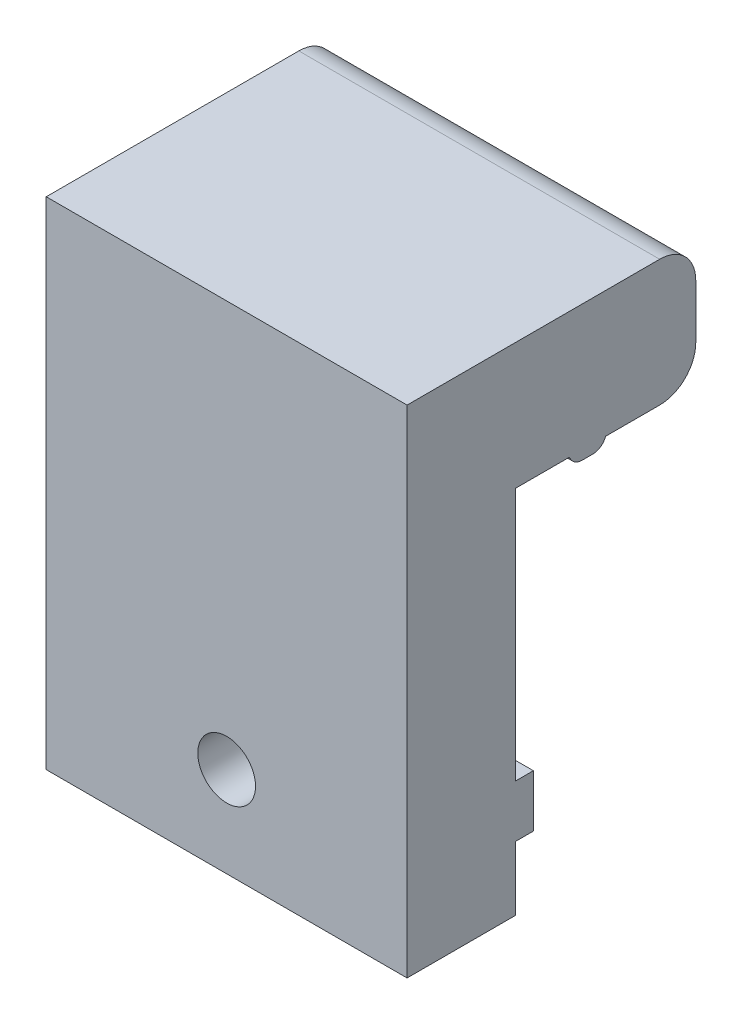
SolidWorks part; units mm, degrees
ref_plane "Front Plane" through (0, 0, 0) normal (0, 0, 1) x (1, 0, 0)
ref_plane "Top Plane" through (0, 0, 0) normal (0, 1, 0) x (1, 0, 0)
ref_plane "Right Plane" through (0, 0, 0) normal (1, 0, 0) x (0, 0, -1)
sketch "Esquisse1" plane through (0, 0, 0) normal (0, 0, 1) x (1, 0, 0)
  line L0 (-10, -13.75) -> (10, -13.75)
  line L1 (10, -13.75) -> (10, 13.75)
  line L2 (10, 13.75) -> (-10, 13.75)
  line L3 (-10, 13.75) -> (-10, -13.75)
  point P3 (0, 13.75)
  point P7 (-10, 0)
  dimension "D1" = 20
  dimension "D2" = 27.5
extrude "Boss.-Extru.1" add sketch "Esquisse1" along normal blind 6
sketch "Esquisse2" plane through (0, 0, 0) normal (0, 0, -1) x (-1, 0, 0)
  line L0 (10, 13.75) -> (10, -13.75) construction
  line L1 (-10, 13.75) -> (10, 13.75)
  line L2 (-10, 13.75) -> (-10, 6.75)
  line L3 (-10, 6.75) -> (10, 6.75)
  line L4 (10, 13.75) -> (10, 6.75)
  dimension "D1" = 7
extrude "Boss.-Extru.2" add sketch "Esquisse2" along normal blind 10
fillet "Congé2" radius 2 2 edges at (0, 6.75, -10) (0, 13.75, -10)
sketch "Esquisse3" plane through (0, 0, 0) normal (0, 0, -1) x (-1, 0, 0)
  line L0 (-10, -13.75) -> (-10, 6.75) construction
  line L1 (-10, -10.2) -> (10, -10.2)
  line L2 (-10, -10.2) -> (-10, -7.3)
  line L3 (-10, -7.3) -> (10, -7.3)
  line L4 (10, -10.2) -> (10, -7.3)
  line L5 (10, 6.75) -> (10, -13.75) construction
  line L6 (10, -13.75) -> (-10, -13.75) construction
  point P8 (-10, -8.75)
  dimension "D1" = 5
  dimension "D2" = 2.9
extrude "Boss.-Extru.3" add sketch "Esquisse3" along normal blind 1
sketch "Esquisse4" plane through (0, 0, 6) normal (0, 0, 1) x (1, 0, 0)
  line L0 (-10, -13.75) -> (10, -13.75) construction
  circle A0 centre (0, -8.75) radius 1.6
  point P5 (0, -13.75)
  dimension "D1" = 3.2
  dimension "D2" = 5
extrude "Enlèv. mat.-Extru.1" cut sketch "Esquisse4" against normal through all
sketch "Esquisse6" plane through (0, 6.75, 0) normal (0, -1, 0) x (1, 0, 0)
  line L0 (-10, -8) -> (-10, 0) construction
  line L1 (10, -3) -> (-10, -3)
  line L2 (10, -3) -> (10, -5)
  line L3 (10, -5) -> (-10, -5)
  line L4 (-10, -3) -> (-10, -5)
  line L5 (10, -8) -> (10, 0) construction
  point P11 (10, -4)
  point P12 (10, -4)
  dimension "D1" = 2
extrude "Boss.-Extru.5" add sketch "Esquisse6" along normal blind 0.5
fillet "Congé4" radius 0.75 2 edges at (0, 6.25, -5) (0, 6.25, -3)
